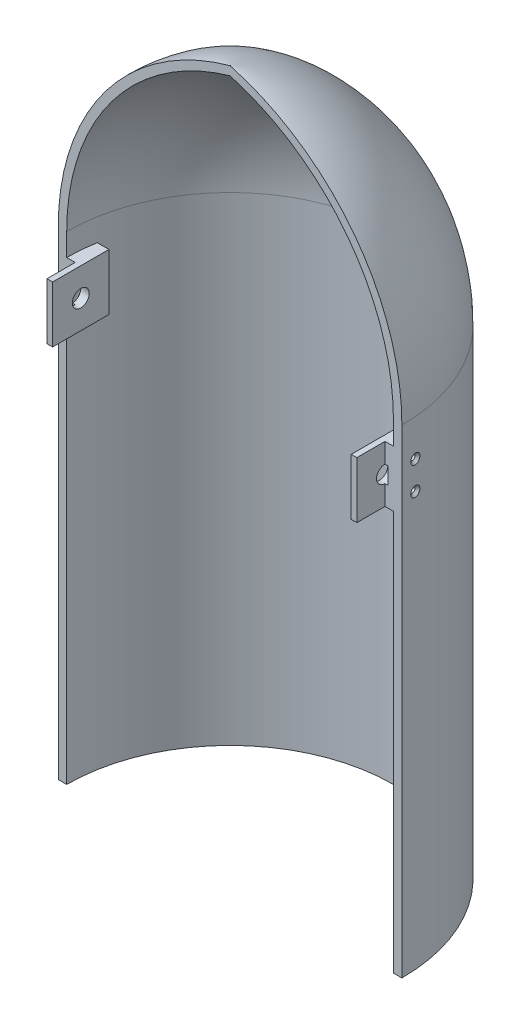
SolidWorks part; units mm, degrees
ref_plane "Front Plane" through (0, 0, 0) normal (0, 0, 1) x (1, 0, 0)
ref_plane "Top Plane" through (0, 0, 0) normal (0, 1, 0) x (1, 0, 0)
ref_plane "Right Plane" through (0, 0, 0) normal (1, 0, 0) x (0, 0, -1)
sketch "Sketch1" plane through (0, 0, 0) normal (0, 0, 1) x (1, 0, 0)
  line L4 (61, 170) -> (61, 0)
  line L5 (0, 246.8846) -> (0, 250)
  line L9 (58, 0) -> (61, 0)
  line L10 (0, 0) -> (0, 250) construction
  line L15 (58, 0) -> (58, 170) construction
  line L16 (61, 0) -> (61, 170) construction
  line L19 (58, 170) -> (58, 0)
  arc A0 (61, 170) -> (0, 250) centre (-21.959, 170) ccw
  arc A1 (58, 170) -> (0, 246.8846) centre (-21.959, 170) ccw
  arc A8 (58, 170) -> (-0.7941, 247.107) centre (-21.959, 170) ccw construction
  dimension "D2" = 170
  dimension "D3" = 80
  dimension "D5" = 61
  dimension "D4" = 3
revolve "Revolve1" add sketch "Sketch1" angle 180 about L10
sketch "Sketch2" plane through (0, 0, 0) normal (0, 0, 1) x (1, 0, 0)
  line L0 (58, 162) -> (53, 162)
  line L1 (-58, 170) -> (58, 170) construction
  line L2 (53, 162) -> (53, 142)
  line L3 (53, 142) -> (58, 142)
  line L4 (58, 170) -> (58, 0) construction
  line L5 (58, 142) -> (58, 162)
  line L6 (0, 251.6085) -> (0, 170) construction
  line L7 (-58, 142) -> (-58, 162)
  line L8 (-58, 162) -> (-53, 162)
  line L9 (-53, 162) -> (-53, 142)
  line L10 (-53, 142) -> (-58, 142)
  dimension "D1" = 5
  dimension "D2" = 20
  dimension "D3" = 8
extrude "Boss-Extrude1" add sketch "Sketch2" against normal blind 10 and the other way blind 10
sketch "Sketch3" plane through (0, 162, 0) normal (0, 1, 0) x (1, 0, 0)
  line L0 (0, 0) -> (0, -9.2604) construction
  line L1 (58, -10) -> (53, 0) construction
  line L2 (0, 0) -> (61, 0) construction
  line L3 (53, -10) -> (53, 10) construction
  line L4 (53, -10) -> (58, 0) construction
  circle A0 centre (55.5, -5) radius 2.5
  dimension "D1" = 5
sketch "Sketch4" plane through (0, 0, 10) normal (0, 0, 1) x (1, 0, 0)
  line L0 (0, 170) -> (0, 142.6292) construction
  line L1 (-58, 170) -> (58, 170) construction
  line L2 (55.5, 142) -> (55.5, 162) construction
  line L3 (53, 142) -> (58, 142) construction
  line L4 (58, 162) -> (53, 162) construction
  line L5 (-55, 162) -> (-56, 162)
  line L6 (55, 142) -> (56, 142)
  line L7 (55, 142) -> (55, 162)
  line L8 (55, 162) -> (56, 162)
  line L10 (55, 142) -> (56, 162) construction
  line L11 (55, 162) -> (56, 142) construction
  line L12 (-55, 142) -> (-56, 142)
  line L13 (-55, 142) -> (-55, 162)
  line L15 (56, 162) -> (58, 162)
  line L16 (58, 162) -> (58, 142)
  line L17 (58, 142) -> (56, 142)
  line L18 (-58, 142) -> (-56, 142)
  line L19 (-58, 162) -> (-58, 142)
  line L20 (-56, 162) -> (-58, 162)
  point P11 (55.5, 152)
  dimension "D1" = 1
extrude "Cut-Extrude1" cut sketch "Sketch4" against normal blind 10
hole_wizard "CSK for M1.6 Countersunk Flat Head Screw2" positions "3DSketch2" profile "Sketch8" countersink size "M1.6" standard "ISO"
sketch3d "3DSketch2"
  line L0 (61, 0, 0) -> (61, 170, 0) construction
  line L1 (61, 170, 0) -> (61, 170, -17.1717) construction
  line L2 (61, 170, 0) -> (61, 170, -17.1717) construction
  line L4 (-61, 170, 0) -> (-61, 170, -37.0841) construction
  line L6 (-61, 0, 0) -> (-61, 170, 0) construction
  point P0 (60.7951, 157.0016, -4.9958)
  point P2 (60.7951, 147.0016, -4.9958)
  point P4 (-60.7951, 147.0016, -4.9958)
  point P6 (-60.7951, 157.0016, -4.9958)
  dimension "D1" = 5
  dimension "D2" = 13
  dimension "D3" = 10
  dimension "D4" = 13
  dimension "D5" = 10
  dimension "D6" = 5
sketch "Sketch8" plane through (60.7951, 157.0016, -4.9958) normal (0, 1, 0) x (-0.0819, 0, -0.9966)
  line L0 (0, 0) -> (0, 5.5408)
  line L1 (0, 5.5408) -> (0.9, 5)
  line L2 (0.9, 5) -> (0.9, 0.9)
  line L3 (0.9, 0.9) -> (1.8, 0)
  line L5 (1.8, 0) -> (0, 0)
  line L6 (-0.9, 0.9) -> (-1.8, 0) construction
  line L10 (0, 5.5408) -> (-0.9, 5) construction
  line L11 (0, -6.35) -> (0, 107.95) construction
  dimension "Hole Dia." = 1.8
  dimension "Hole Depth" = 5
  dimension "Near C'Sink Dia." = 3.6
  dimension "Near C'Sink Angle" = 90
  dimension "Drill Angle" = 118
sketch "Sketch9" plane through (-53, 0, 0) normal (1, 0, 0) x (0, 0, -1)
  line L0 (0, 162) -> (0, 142) construction
  line L1 (-10, 162) -> (10, 162) construction
  line L2 (-10, 142) -> (10, 142) construction
  circle A0 centre (0, 152) radius 3
  dimension "D1" = 6
extrude "Cut-Extrude2" cut sketch "Sketch9" against normal blind 3
sketch "Sketch10" plane through (53, 0, 0) normal (-1, 0, 0) x (0, 0, 1)
  line L0 (0, 162) -> (0, 142) construction
  line L1 (10, 162) -> (-10, 162) construction
  line L2 (10, 142) -> (-10, 142) construction
  circle A0 centre (0, 152) radius 3
  dimension "D1" = 6
extrude "Cut-Extrude3" cut sketch "Sketch10" against normal blind 3
